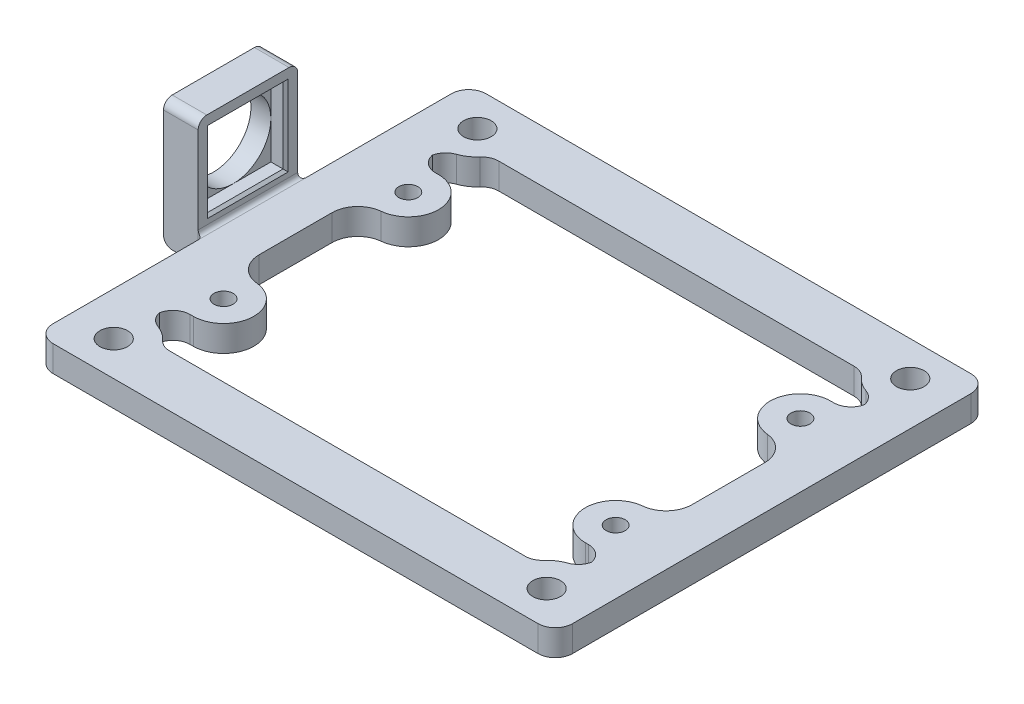
SolidWorks part; units mm, degrees
ref_plane "前视基准面" through (0, 0, 0) normal (0, 0, 1) x (1, 0, 0)
ref_plane "上视基准面" through (0, 0, 0) normal (0, 1, 0) x (1, 0, 0)
ref_plane "右视基准面" through (0, 0, 0) normal (1, 0, 0) x (0, 0, -1)
sketch "草图1" plane through (0, 0, 0) normal (0, 1, 0) x (1, 0, 0)
  line L0 (0, 0) -> (0, 10.1292) construction
  line L1 (-30, -25) -> (30, -25)
  line L2 (-30, -25) -> (-30, -5.75)
  line L3 (-30, 25) -> (30, 25)
  line L4 (30, -25) -> (30, 25)
  line L5 (-30, -25) -> (30, 25) construction
  line L6 (-30, 25) -> (30, -25) construction
  line L7 (0, 0) -> (9.2435, 0) construction
  line L8 (-25, -7.17) -> (-25, 7.17)
  line L9 (-25, 7.17) -> (-22.645, 7.17)
  line L10 (-22.645, 14.17) -> (-25, 14.17)
  line L11 (-25, 14.17) -> (-25, 17)
  line L12 (21.5359, 19) -> (-21.5359, 19)
  line L13 (25, 14.17) -> (25, 17)
  line L14 (22.645, 14.17) -> (25, 14.17)
  line L15 (25, 7.17) -> (22.645, 7.17)
  line L16 (25, -7.17) -> (25, 7.17)
  line L17 (25, -7.17) -> (22.645, -7.17)
  line L18 (22.645, -14.17) -> (25, -14.17)
  line L19 (25, -14.17) -> (25, -17)
  line L20 (21.5359, -19) -> (-21.5359, -19)
  line L21 (-25, -14.17) -> (-25, -17)
  line L22 (-22.645, -14.17) -> (-25, -14.17)
  line L23 (-25, -7.17) -> (-22.645, -7.17)
  line L24 (-30, 5.75) -> (-34.5, 5.75)
  line L25 (-34.5, 5.75) -> (-34.5, -5.75)
  line L26 (-30, -5.75) -> (-34.5, -5.75)
  line L27 (-30, 5.75) -> (-30, 25)
  circle A0 centre (-25, 21) radius 1.6
  circle A1 centre (25, 21) radius 1.6
  circle A2 centre (25, -21) radius 1.6
  circle A3 centre (-25, -21) radius 1.6
  circle A4 centre (-22.645, 10.67) radius 1.1
  circle A5 centre (22.645, 10.67) radius 1.1
  circle A6 centre (-22.645, -10.67) radius 1.1
  circle A7 centre (22.645, -10.67) radius 1.1
  arc A8 (-22.645, 7.17) -> (-22.645, 14.17) centre (-22.645, 10.67) ccw
  arc A9 (-25, 17) -> (-21.5359, 19) centre (-25, 21) ccw
  arc A10 (25, 17) -> (21.5359, 19) centre (25, 21) cw
  arc A11 (22.645, 7.17) -> (22.645, 14.17) centre (22.645, 10.67) cw
  arc A12 (22.645, -7.17) -> (22.645, -14.17) centre (22.645, -10.67) ccw
  arc A13 (25, -17) -> (21.5359, -19) centre (25, -21) ccw
  arc A14 (-25, -17) -> (-21.5359, -19) centre (-25, -21) cw
  arc A15 (-22.645, -7.17) -> (-22.645, -14.17) centre (-22.645, -10.67) cw
  point P0 (0, 0)
  point P37 (0, 19)
  point P44 (25, 0)
  point P55 (-25, 0)
  point P58 (-34.5, 0)
  dimension "D3" = 3.2
  dimension "D4" = 50
  dimension "D5" = 42
  dimension "D6" = 2.2
  dimension "D7" = 45.29
  dimension "D8" = 21.34
  dimension "D10" = 3.5
  dimension "D12" = 4
  dimension "D1" = 60
  dimension "D2" = 50
  dimension "D9" = 5
  dimension "D11" = 6
  dimension "D13" = 11.5
  dimension "D14" = 4.5
extrude "凸台-拉伸1" add sketch "草图1" along normal blind 3
sketch "草图2" plane through (0, 3, 0) normal (0, 1, 0) x (1, 0, 0)
  line L0 (-34.5, -5.75) -> (-30, -5.75) construction
  line L1 (-34.5, 5.75) -> (-34.5, -5.75) construction
  line L2 (-30, 5.75) -> (-34.5, 5.75) construction
  line L3 (-34.5, -5.75) -> (-30.5, -5.75)
  line L4 (-34.5, 5.75) -> (-34.5, -5.75)
  line L5 (-30.5, 5.75) -> (-34.5, 5.75)
  line L6 (-30.5, -5.75) -> (-30.5, 5.75)
  dimension "D1" = 4
extrude "凸台-拉伸2" add sketch "草图2" along normal blind 11.5
sketch "草图3" plane through (-30.5, 0, 0) normal (1, 0, 0) x (0, 0, -1)
  line L0 (-5.75, 3) -> (5.75, 3) construction
  line L1 (-5.75, 14.5) -> (-5.75, 3) construction
  line L2 (5.75, 14.5) -> (5.75, 3) construction
  line L3 (-5.75, 14.5) -> (5.75, 14.5) construction
  line L4 (-5.75, 3) -> (5.75, 3)
  line L5 (-5.75, 14.5) -> (-5.75, 3)
  line L6 (5.75, 14.5) -> (5.75, 3)
  line L7 (-5.75, 14.5) -> (5.75, 14.5)
  line L9 (4.35, 13.1) -> (-4.35, 13.1)
  line L10 (4.35, 13.1) -> (4.35, 4.4)
  line L11 (4.35, 4.4) -> (-4.35, 4.4)
  line L12 (-4.35, 13.1) -> (-4.35, 4.4)
  circle A0 centre (0, 8.75) radius 4.35
  line M10 (5.75, 3) -> (5.75, 14.5)
  dimension "D1" = 8.7
  dimension "D2" = 1.4
  dimension "D3" = 1.4
extrude "切除-拉伸2" cut sketch "草图3" against normal through all contours A0 M10 region at (-30.5, 8.75, 0)
extrude "切除-拉伸3" cut sketch "草图3<4>" against normal blind 1.7 contours A0 L10 L9 | A0 L9 L12 | A0 L12 L11 | A0 L11 L10 region at (-30.5, 12.1283, -3.3783) region at (-30.5, 12.1283, 3.3783) region at (-30.5, 5.3717, -3.3783) region at (-30.5, 5.3717, 3.3783)
sketch "草图3<4>" plane through (-30.5, 0, 0) normal (1, 0, 0) x (0, 0, -1) same geometry as "草图3"
fillet "圆角1" radius 2 4 edges at (30, 1.5, 25) (30, 1.5, -25) (-30, 1.5, 25) (-30, 1.5, -25)
fillet "圆角2" radius 3 4 edges at (25, 1.5, -7.17) (25, 1.5, 7.17) (-25, 1.5, 7.17) (-25, 1.5, -7.17)
fillet "圆角4" radius 2 12 edges at (-25, 1.5, -14.17) (-25, 1.5, -17) (-21.5359, 1.5, -19) (-25, 1.5, 14.17) (-25, 1.5, 17) (-21.5359, 1.5, 19) (21.5359, 1.5, 19) (25, 1.5, 17) (25, 1.5, 14.17) (21.5359, 1.5, -19) (25, 1.5, -17) (25, 1.5, -14.17)
fillet "圆角6" radius 1 2 edges at (-32.5, 14.5, -5.75) (-32.5, 14.5, 5.75)
fillet "圆角7" radius 1 1 edges at (-34.5, 0, 0)
fillet "圆角8" radius 0.5 1 edges at (-30.5, 3, 0)
fillet "圆角9" radius 0.5 2 edges at (-30, 1.5, -5.75) (-30, 1.5, 5.75)
chamfer "倒角1" distance 0.3 angle 45 4 edges at (-30.5, 4.4, 0) (-30.5, 8.75, 4.35) (-30.5, 8.75, -4.35) (-30.5, 13.1, 0)
